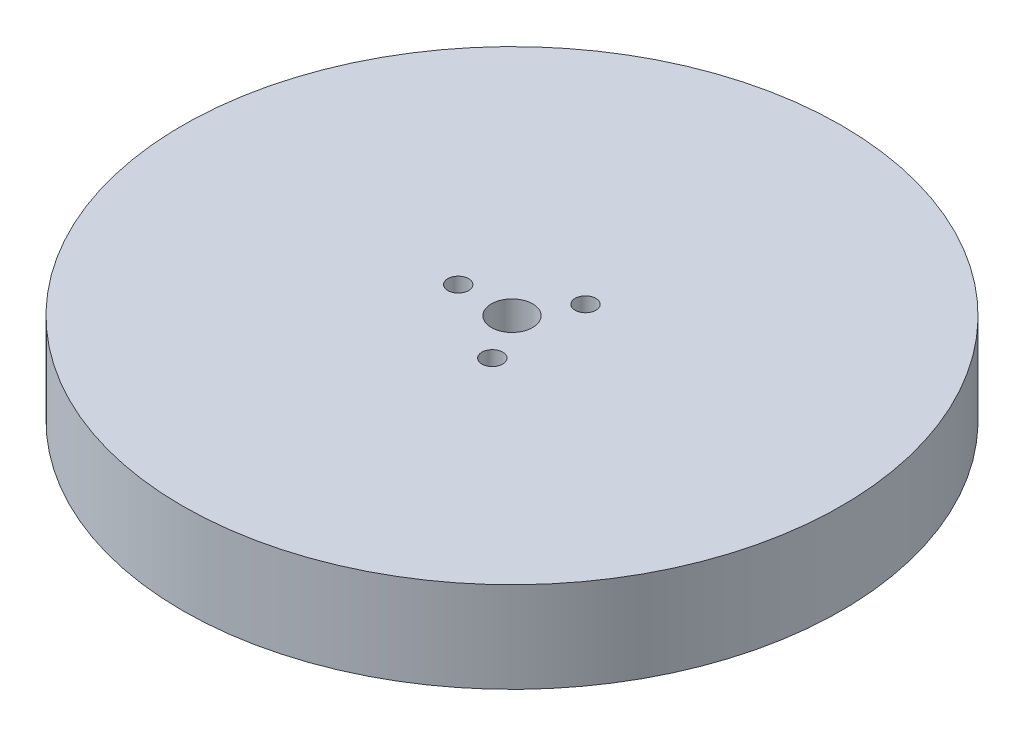
SolidWorks part; units mm, degrees
ref_plane "Front Plane" through (0, 0, 0) normal (0, 0, 1) x (1, 0, 0)
ref_plane "Top Plane" through (0, 0, 0) normal (0, 1, 0) x (1, 0, 0)
ref_plane "Right Plane" through (0, 0, 0) normal (1, 0, 0) x (0, 0, -1)
sketch "Sketch1" plane through (0, 0, 0) normal (0, 1, 0) x (1, 0, 0)
  circle A0 centre (0, 0) radius 80
  dimension "FLANGE_OD" = 160
extrude "Boss-Extrude1" add sketch "Sketch1" along normal blind 22
sketch "Sketch2" plane through (0, 0, 0) normal (0, 1, 0) x (1, 0, 0)
  circle A0 centre (0, 0) radius 5
  dimension "BORE_D" = 10
extrude "Cut-Extrude1" cut sketch "Sketch2" along normal through all
sketch "Sketch3" plane through (0, 22, 0) normal (0, 1, 0) x (1, 0, 0)
  circle A0 centre (0, 0) radius 13.0589 construction
  circle A1 centre (-13.0589, 0) radius 2.52
  dimension "BOLT_D" = 5.0401
  dimension "BOLT_PCD" = 26.1178
extrude "Cut-Extrude2" cut sketch "Sketch3" against normal blind 17.0748
pattern_circular "CirPattern1" count 3 over 360 about axis through (0, 0, 0) along (0, 1, 0) of "Cut-Extrude2"
